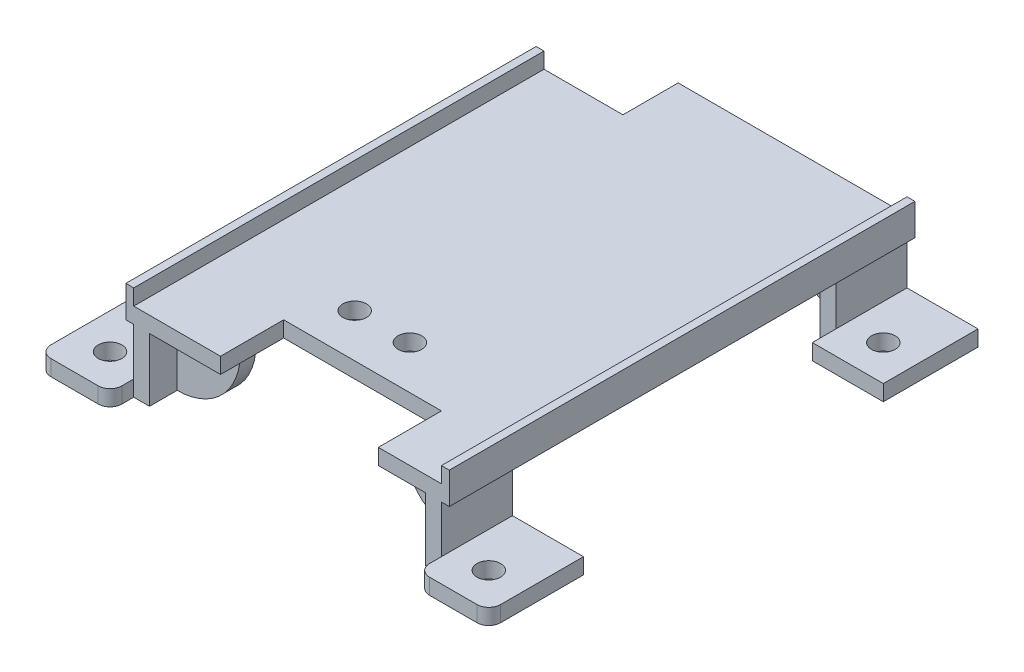
SolidWorks part; units mm, degrees
ref_plane "Front Plane" through (0, 0, 0) normal (0, 0, 1) x (1, 0, 0)
ref_plane "Top Plane" through (0, 0, 0) normal (0, 1, 0) x (1, 0, 0)
ref_plane "Right Plane" through (0, 0, 0) normal (1, 0, 0) x (0, 0, -1)
sketch "Sketch1" plane through (0, 0, 0) normal (0, 1, 0) x (1, 0, 0)
  line L1 (0, 0) -> (57, 0)
  line L2 (0, 0) -> (0, 59)
  line L3 (0, 59) -> (57, 59)
  line L4 (57, 0) -> (57, 59)
  dimension "D1" = 57
  dimension "D2" = 59
extrude "Boss-Extrude1" add sketch "Sketch1" along normal blind 10
sketch "Sketch2" plane through (57, 0, 0) normal (1, 0, 0) x (0, 0, -1)
  line L0 (0, 10) -> (59, 10) construction
  line L1 (9, 10) -> (50, 10)
  line L2 (9, 10) -> (9, 0)
  line L3 (9, 0) -> (50, 0)
  line L4 (50, 10) -> (50, 0)
  line L5 (0, 0) -> (59, 0) construction
  line L6 (0, 10) -> (0, 0) construction
  dimension "D1" = 9
  dimension "D2" = 9
extrude "Cut-Extrude1" cut sketch "Sketch2" against normal blind 9
sketch "Sketch4" plane through (0, 10, 0) normal (0, 1, 0) x (1, 0, 0)
  line L0 (0, 59) -> (0, 0) construction
  line L1 (0, 52) -> (10, 52)
  line L2 (0, 52) -> (0, 59)
  line L3 (0, 59) -> (10, 59)
  line L4 (10, 52) -> (10, 59)
  line L5 (57, 59) -> (0, 59) construction
  dimension "D1" = 10
  dimension "D2" = 7
extrude "Cut-Extrude3" cut sketch "Sketch4" against normal through all
sketch "Sketch5" plane through (0, 0, 0) normal (-1, 0, 0) x (0, 0, 1)
  line L0 (-52, 10) -> (0, 10) construction
  line L1 (-43, 10) -> (-9, 10)
  line L2 (-43, 10) -> (-43, 0)
  line L3 (-43, 0) -> (-9, 0)
  line L4 (-9, 10) -> (-9, 0)
  line L5 (-52, 0) -> (0, 0) construction
  line L6 (-52, 0) -> (-52, 10) construction
  line L7 (0, 10) -> (0, 0) construction
  dimension "D1" = 9
  dimension "D2" = 9
extrude "Cut-Extrude4" cut sketch "Sketch5" against normal blind 9
sketch "Sketch6" plane through (0, 10, 0) normal (0, 1, 0) x (1, 0, 0)
  line L0 (0, 0) -> (57, 0) construction
  line L1 (9, 0) -> (48, 0)
  line L2 (9, 0) -> (9, 59)
  line L3 (9, 59) -> (48, 59)
  line L4 (48, 0) -> (48, 59)
  line L5 (57, 59) -> (10, 59) construction
sketch "Sketch7" plane through (0, 0, 0) normal (0, 0, 1) x (1, 0, 0)
  line L0 (0, 0) -> (57, 0) construction
  line L1 (9, 10) -> (48, 10)
  line L2 (9, 10) -> (9, 0)
  line L3 (9, 0) -> (48, 0)
  line L4 (48, 10) -> (48, 0)
sketch "Sketch8" plane through (0, 0, 0) normal (0, 0, 1) x (1, 0, 0)
  line L0 (9, 10) -> (48, 10) construction
  line L1 (20, 10) -> (40, 10)
  line L2 (20, 10) -> (20, 0)
  line L3 (20, 0) -> (40, 0)
  line L4 (40, 10) -> (40, 0)
  line L5 (9, 0) -> (48, 0) construction
  line L6 (9, 10) -> (9, 0) construction
  point P8 (20, 5)
  dimension "D1" = 11
  dimension "D2" = 20
extrude "Cut-Extrude5" cut sketch "Sketch8" against normal blind 8
sketch "Sketch9" plane through (0, 0, 0) normal (0, -1, 0) x (-1, 0, 0)
  line L0 (-57, 59) -> (-10, 59) construction
  line L1 (-11, 0) -> (-46, 0)
  line L2 (-11, 0) -> (-11, 59)
  line L3 (-11, 59) -> (-46, 59)
  line L4 (-46, 0) -> (-46, 59)
  dimension "D1" = 35
  dimension "D2" = 2
extrude "Cut-Extrude6" cut sketch "Sketch9" against normal blind 8
sketch "Sketch10" plane through (0, 10, 0) normal (0, 1, 0) x (1, 0, 0)
  line L1 (10, 52) -> (19, 52)
  line L2 (10, 52) -> (10, 59)
  line L3 (10, 59) -> (19, 59)
  line L4 (19, 52) -> (19, 59)
  dimension "D1" = 9
extrude "Cut-Extrude7" cut sketch "Sketch10" against normal through all
sketch "Sketch11" plane through (0, 10, 0) normal (0, 1, 0) x (1, 0, 0)
  line L1 (48, 0) -> (57, 0)
  line L2 (48, 0) -> (48, 9)
  line L3 (48, 9) -> (57, 9)
  line L4 (57, 0) -> (57, 9)
extrude "Cut-Extrude8" cut sketch "Sketch11" against normal blind 8
sketch "Sketch12" plane through (0, 10, 0) normal (0, 1, 0) x (1, 0, 0)
  line L1 (48, 59) -> (57, 59)
  line L2 (48, 59) -> (48, 50)
  line L3 (48, 50) -> (57, 50)
  line L4 (57, 59) -> (57, 50)
extrude "Cut-Extrude9" cut sketch "Sketch12" against normal blind 8
sketch "Sketch13" plane through (0, 10, 0) normal (0, 1, 0) x (1, 0, 0)
  line L1 (0, 52) -> (9, 52)
  line L2 (0, 52) -> (0, 43)
  line L3 (0, 43) -> (9, 43)
  line L4 (9, 52) -> (9, 43)
extrude "Cut-Extrude10" cut sketch "Sketch13" against normal blind 8
sketch "Sketch14" plane through (0, 10, 0) normal (0, 1, 0) x (1, 0, 0)
  line L1 (9, 0) -> (0, 0)
  line L2 (9, 0) -> (9, 9)
  line L3 (9, 9) -> (0, 9)
  line L4 (0, 0) -> (0, 9)
extrude "Cut-Extrude11" cut sketch "Sketch14" against normal blind 8
sketch "Sketch15" plane through (0, 0, 0) normal (0, -1, 0) x (-1, 0, 0)
  line L0 (-46, 59) -> (-46, 0) construction
  line L1 (-48, 9) -> (-46, 9)
  line L2 (-48, 9) -> (-48, 50)
  line L3 (-48, 50) -> (-46, 50)
  line L4 (-46, 9) -> (-46, 50)
extrude "Cut-Extrude12" cut sketch "Sketch15" against normal blind 8
sketch "Sketch16" plane through (0, 0, 0) normal (0, -1, 0) x (-1, 0, 0)
  line L0 (-11, 0) -> (-11, 52) construction
  line L1 (-9, 9) -> (-11, 9)
  line L2 (-9, 9) -> (-9, 43)
  line L3 (-9, 43) -> (-11, 43)
  line L4 (-11, 9) -> (-11, 43)
extrude "Cut-Extrude13" cut sketch "Sketch16" against normal blind 8
sketch "Sketch31" plane through (11, 0, 0) normal (1, 0, 0) x (0, 0, -1)
  line L0 (0, 8) -> (9, 8) construction
  line L1 (3.5, 8) -> (5.5, 8)
  line L2 (3.5, 8) -> (3.5, 0)
  line L3 (3.5, 0) -> (5.5, 0)
  line L4 (5.5, 8) -> (5.5, 0)
  line L5 (0, 0) -> (9, 0) construction
  line L6 (0, 8) -> (0, 0) construction
  line L7 (9, 8) -> (9, 0) construction
  point P10 (0, 4)
  dimension "D1" = 3.5
  dimension "D2" = 3.5
revolve "Revolve3" add sketch "Sketch31" angle 90 about L1 reverse direction yes
sketch "Sketch32" plane through (11, 0, 0) normal (1, 0, 0) x (0, 0, -1)
  line L0 (43, 8) -> (52, 8) construction
  line L1 (46.5, 8) -> (48.5, 8)
  line L2 (46.5, 8) -> (46.5, 0)
  line L3 (46.5, 0) -> (48.5, 0)
  line L4 (48.5, 8) -> (48.5, 0)
  line L5 (43, 0) -> (52, 0) construction
  line L6 (43, 8) -> (43, 0) construction
  line L7 (52, 0) -> (52, 8) construction
  dimension "D1" = 3.5
  dimension "D2" = 3.5
revolve "Revolve4" add sketch "Sketch32" angle 90 about L1 reverse direction yes
sketch "Sketch33" plane through (0, 8, 0) normal (0, -1, 0) x (1, 0, 0)
  line L0 (40, 0) -> (40, -8) construction
  line L1 (40, -3.5) -> (46, -3.5)
  line L2 (40, -3.5) -> (40, -5.5)
  line L3 (40, -5.5) -> (46, -5.5)
  line L4 (46, -3.5) -> (46, -5.5)
  line L5 (46, -9) -> (46, 0) construction
  line L6 (46, 0) -> (40, 0) construction
  dimension "D1" = 3.5
  dimension "D2" = 3.5
revolve "Revolve5" add sketch "Sketch33" angle 90 about L4 reverse direction yes
sketch "Sketch34" plane through (46, 0, 0) normal (-1, 0, 0) x (0, 0, 1)
  line L0 (-59, 0) -> (-50, 0) construction
  line L1 (-53.5, 0) -> (-55.5, 0)
  line L2 (-53.5, 0) -> (-53.5, 8)
  line L3 (-53.5, 8) -> (-55.5, 8)
  line L4 (-55.5, 0) -> (-55.5, 8)
  line L5 (-59, 8) -> (-50, 8) construction
  line L6 (-50, 8) -> (-50, 0) construction
  line L7 (-59, 8) -> (-59, 0) construction
  point P10 (-55.5, 4)
  dimension "D1" = 3.5
  dimension "D2" = 3.5
revolve "Revolve6" add sketch "Sketch34" angle 90 about L3
sketch "Sketch42" plane through (0, 10, 0) normal (0, 1, 0) x (1, 0, 0)
  line L0 (9, 0) -> (9, 52) construction
  line L1 (48, 59) -> (48, 0) construction
  line L2 (48, 59) -> (19, 59) construction
  circle A0 centre (23.5, 13.5) radius 1.5
  circle A1 centre (30.5, 13.5) radius 1.5
  dimension "D5" = 3
  dimension "D6" = 3
  dimension "D1" = 14.5
  dimension "D2" = 17.5
  dimension "D3" = 45.5
  dimension "D4" = 45.5
extrude "Cut-Extrude15" cut sketch "Sketch42" against normal through all
sketch "Sketch46" plane through (48, 0, 0) normal (1, 0, 0) x (0, 0, -1)
  line L0 (59, 2) -> (59, 10) construction
  line L1 (0, 10) -> (59, 10)
  line L2 (0, 10) -> (0, 8)
  line L3 (0, 8) -> (59, 8)
  line L4 (59, 10) -> (59, 8)
extrude "Boss-Extrude3" add sketch "Sketch46" along normal blind 1
sketch "Sketch47" plane through (0, 10, 0) normal (0, 1, 0) x (1, 0, 0)
  line L0 (40, 0) -> (49, 0) construction
  line L1 (49, 59) -> (48, 59)
  line L2 (49, 59) -> (49, 0)
  line L3 (49, 0) -> (48, 0)
  line L4 (48, 59) -> (48, 0)
  dimension "D1" = 1
extrude "Boss-Extrude4" add sketch "Sketch47" along normal blind 2
sketch "Sketch48" plane through (9, 0, 0) normal (-1, 0, 0) x (0, 0, 1)
  line L1 (-52, 10) -> (0, 10)
  line L2 (-52, 10) -> (-52, 8)
  line L3 (-52, 8) -> (0, 8)
  line L4 (0, 10) -> (0, 8)
extrude "Boss-Extrude5" add sketch "Sketch48" along normal blind 1
sketch "Sketch49" plane through (0, 10, 0) normal (0, 1, 0) x (1, 0, 0)
  line L0 (8, 0) -> (20, 0) construction
  line L1 (8, 52) -> (9, 52)
  line L2 (8, 52) -> (8, 0)
  line L3 (8, 0) -> (9, 0)
  line L4 (9, 52) -> (9, 0)
  dimension "D1" = 1
extrude "Boss-Extrude6" add sketch "Sketch49" along normal blind 2
sketch "Sketch50" plane through (0, 0, 0) normal (0, 0, 1) x (1, 0, 0)
  line L0 (0, 0) -> (11, 0) construction
  line L1 (0, 2) -> (9, 2)
  line L2 (0, 2) -> (0, 0)
  line L3 (0, 0) -> (9, 0)
  line L4 (9, 2) -> (9, 0)
  line L6 (48, 2) -> (57, 2)
  line L7 (48, 2) -> (48, 0)
  line L8 (48, 0) -> (57, 0)
  line L9 (57, 2) -> (57, 0)
extrude "Boss-Extrude7" add sketch "Sketch50" along normal blind 3
sketch "Sketch51" plane through (0, 0, -43) normal (0, 0, 1) x (1, 0, 0)
  line L1 (9, 2) -> (0, 2)
  line L2 (9, 2) -> (9, 0)
  line L3 (9, 0) -> (0, 0)
  line L4 (0, 2) -> (0, 0)
extrude "Boss-Extrude8" add sketch "Sketch51" along normal blind 3
sketch "Sketch52" plane through (0, 0, -50) normal (0, 0, 1) x (1, 0, 0)
  line L1 (48, 2) -> (57, 2)
  line L2 (48, 2) -> (48, 0)
  line L3 (48, 0) -> (57, 0)
  line L4 (57, 2) -> (57, 0)
extrude "Boss-Extrude9" add sketch "Sketch52" along normal blind 3
sketch "Sketch53" plane through (0, 2, 0) normal (0, 1, 0) x (1, 0, 0)
  line L0 (9, 52) -> (0, 52) construction
  line L1 (0, 52) -> (0, 40) construction
  line L2 (57, 59) -> (48, 59) construction
  line L3 (57, 47) -> (57, 59) construction
  line L4 (9, 9) -> (0, 9) construction
  line L5 (0, 9) -> (0, -3) construction
  line L6 (57, 9) -> (48, 9) construction
  line L7 (57, -3) -> (57, 9) construction
  circle A0 centre (4.5, 44.5) radius 1.5
  circle A1 centre (52.5, 51.5) radius 1.5
  circle A2 centre (52.5, 1.5) radius 1.5
  circle A3 centre (4.5, 1.5) radius 1.5
  dimension "D1" = 3
  dimension "D4" = 3
  dimension "D7" = 3
  dimension "D10" = 3
  dimension "D2" = 7.5
  dimension "D3" = 4.5
  dimension "D5" = 7.5
  dimension "D6" = 4.5
  dimension "D8" = 7.5
  dimension "D9" = 4.5
  dimension "D11" = 7.5
  dimension "D12" = 4.5
extrude "Cut-Extrude16" cut sketch "Sketch53" against normal through all
fillet "Fillet2" radius 1.5 4 edges at (57, 1, 3) (48, 1, 3) (9, 1, 3) (0, 1, 3)
